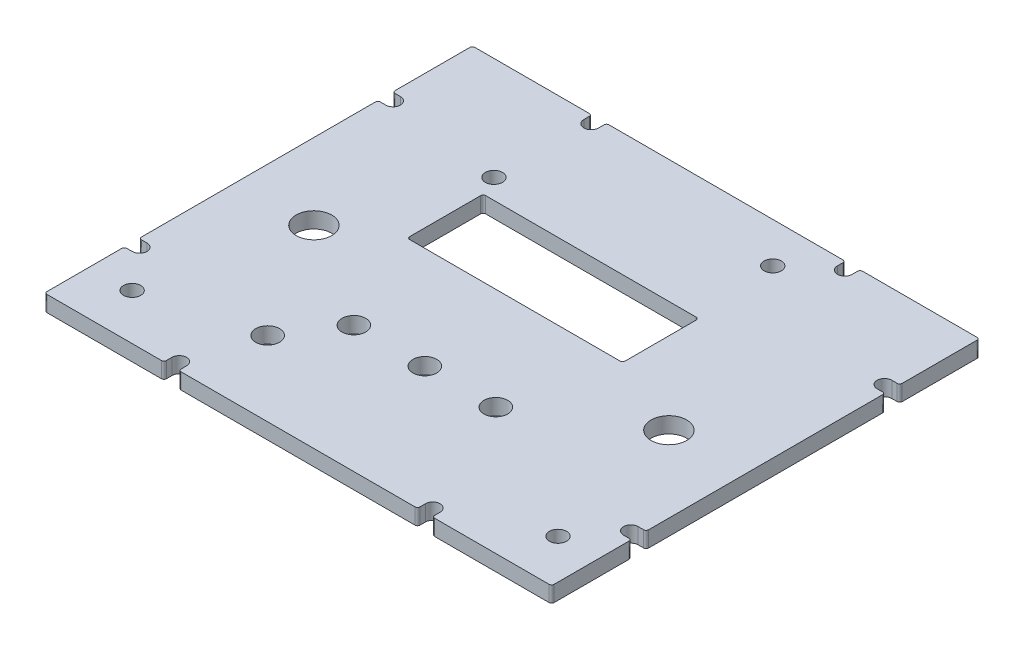
SolidWorks part; units mm, degrees
ref_plane "Front Plane" through (0, 0, 0) normal (0, 0, 1) x (1, 0, 0)
ref_plane "Top Plane" through (0, 0, 0) normal (0, 1, 0) x (1, 0, 0)
ref_plane "Right Plane" through (0, 0, 0) normal (1, 0, 0) x (0, 0, -1)
sketch "Sketch1" plane through (0, 0, 0) normal (0, 1, 0) x (1, 0, 0)
  line L1 (-50.8, -42.8625) -> (50.8, -42.8625)
  line L2 (-50.8, -42.8625) -> (-50.8, 42.8625)
  line L3 (-50.8, 42.8625) -> (50.8, 42.8625)
  line L4 (50.8, -42.8625) -> (50.8, 42.8625)
  line L5 (-50.8, -42.8625) -> (50.8, 42.8625) construction
  line L6 (-50.8, 42.8625) -> (50.8, -42.8625) construction
  point P0 (0, 0)
  dimension "D1" = 101.6
  dimension "D2" = 85.725
extrude "Boss-Extrude1" add sketch "Sketch1" along normal blind 3.175
hole_wizard "#29 (0.136) Diameter Hole1" positions "Sketch2" profile "Sketch3" hole size "#29" standard "ANSI Inch" end condition through all
sketch "Sketch2" plane through (0, 3.175, 0) normal (0, 1, 0) x (1, 0, 0)
  point P0 (-25.8318, 22.2123)
  point P3 (17.4498, 34.7853)
  point P6 (42.8498, -33.6423)
  point P9 (-42.4688, -33.6423)
sketch "Sketch3" plane through (-25.8318, 3.175, -22.2123) normal (1, 0, 0) x (0, 0, 1)
  line L0 (0, 0) -> (0, 3.175)
  line L1 (0, 3.175) -> (1.7272, 3.175)
  line L2 (1.7272, 3.175) -> (1.7272, 0)
  line L5 (1.7272, 0) -> (0, 0)
  line L11 (0, -6.35) -> (0, 107.95) construction
  dimension "Thru Hole Dia." = 3.4544
  dimension "Thru Hole Depth" = 3.175
hole_wizard "9/32 (0.28125) Diameter Hole1" positions "Sketch4" profile "Sketch5" hole size "9/32" standard "ANSI Inch" end condition through all
sketch "Sketch4" plane through (0, 3.175, 0) normal (0, 1, 0) x (1, 0, 0)
  point P0 (-35.56, -4.1275)
  point P3 (35.56, -4.1275)
sketch "Sketch5" plane through (-35.56, 3.175, 4.1275) normal (1, 0, 0) x (0, 0, 1)
  line L0 (0, 0) -> (0, 3.175)
  line L1 (0, 3.175) -> (3.5719, 3.175)
  line L2 (3.5719, 3.175) -> (3.5719, 0)
  line L5 (3.5719, 0) -> (0, 0)
  line L11 (0, -6.35) -> (0, 107.95) construction
  dimension "Thru Hole Dia." = 7.1437
  dimension "Thru Hole Depth" = 3.175
hole_wizard "3/16 (0.1875) Diameter Hole1" positions "Sketch6" profile "Sketch7" hole size "3/16" standard "ANSI Inch" end condition through all
sketch "Sketch6" plane through (0, 3.175, 0) normal (0, 1, 0) x (1, 0, 0)
  point P13 (-14.224, -17.4625)
  point P15 (0, -17.4625)
  point P17 (14.224, -17.4625)
  point P19 (-21.082, -27.8765)
sketch "Sketch7" plane through (-14.224, 3.175, 17.4625) normal (1, 0, 0) x (0, 0, 1)
  line L0 (0, 0) -> (0, 3.175)
  line L1 (0, 3.175) -> (2.3812, 3.175)
  line L2 (2.3812, 3.175) -> (2.3812, 0)
  line L5 (2.3812, 0) -> (0, 0)
  line L11 (0, -6.35) -> (0, 107.95) construction
  dimension "Thru Hole Dia." = 4.7625
  dimension "Thru Hole Depth" = 3.175
sketch "Sketch8" plane through (0, 3.175, 0) normal (0, 1, 0) x (1, 0, 0)
  line L0 (-24.003, 18.2245) -> (19.177, 18.2245)
  line L5 (19.177, 18.2245) -> (19.177, 2.9845)
  line L6 (-24.003, 2.9845) -> (19.177, 2.9845)
  line L7 (-24.003, 18.2245) -> (-24.003, 2.9845)
  circle A0 centre (-25.8318, 22.2123) radius 1.7272 construction
  dimension "D1" = 1.8288
  dimension "D2" = 45.0088
  dimension "D3" = 3.9878
  dimension "D4" = 19.2278
extrude "Cut-Extrude1" cut sketch "Sketch8" against normal through all
sketch "Sketch9" plane through (0, 3.175, 0) normal (0, 1, 0) x (1, 0, 0)
  line L0 (-50.8, 42.8625) -> (50.8, -42.8625) construction
  line L1 (50.8, 42.8625) -> (-50.8, 42.8625) construction
  line L2 (49.2125, -41.275) -> (-49.2125, -41.275) construction
  line L3 (49.2125, -41.275) -> (49.2125, 41.275) construction
  line L4 (49.2125, 41.275) -> (-49.2125, 41.275) construction
  line L5 (-49.2125, -41.275) -> (-49.2125, 41.275) construction
  line L6 (49.2125, -41.275) -> (-49.2125, 41.275) construction
  line L7 (49.2125, 41.275) -> (-49.2125, -41.275) construction
  line L8 (-50.8, 42.8625) -> (-50.8, -42.8625) construction
  line L9 (-49.2125, 26.8732) -> (-50.8, 26.8732)
  line L10 (-49.2125, 23.9268) -> (-50.8, 23.9268)
  line L11 (-50.8, 26.8732) -> (-50.8, 23.9268)
  line L12 (-49.2125, -23.9268) -> (-50.8, -23.9268)
  line L13 (-50.8, -23.9268) -> (-50.8, -26.8732)
  line L14 (-49.2125, -26.8732) -> (-50.8, -26.8732)
  line L15 (0, 0) -> (0, 12.7264) construction
  line L16 (49.2125, -26.8732) -> (50.8, -26.8732)
  line L17 (50.8, -23.9268) -> (50.8, -26.8732)
  line L18 (49.2125, -23.9268) -> (50.8, -23.9268)
  line L19 (50.8, 26.8732) -> (50.8, 23.9268)
  line L20 (49.2125, 23.9268) -> (50.8, 23.9268)
  line L21 (49.2125, 26.8732) -> (50.8, 26.8732)
  line L23 (-24.003, 2.9845) -> (19.177, 2.9845) construction
  arc A0 (-49.2125, 23.9268) -> (-49.2125, 26.8732) centre (-49.2125, 25.4) ccw
  arc A1 (-49.2125, -26.8732) -> (-49.2125, -23.9268) centre (-49.2125, -25.4) ccw
  arc A2 (49.2125, -26.8732) -> (49.2125, -23.9268) centre (49.2125, -25.4) cw
  arc A3 (49.2125, 23.9268) -> (49.2125, 26.8732) centre (49.2125, 25.4) cw
  point P4 (0, 0)
  point P16 (-49.2125, 0)
  dimension "D3" = 25.4
  dimension "D5" = 1.4732
  dimension "D1" = 1.5875
  dimension "D2" = 1.5875
  dimension "D6" = 28.3845
  dimension "D4" = 2
extrude "Cut-Extrude2" cut sketch "Sketch9" against normal through all
fillet "Fillet1" radius 0.508 12 edges at (50.8, 1.5875, -23.9268) (50.8, 1.5875, -26.8732) (50.8, 1.5875, 23.9268) (50.8, 1.5875, 26.8732) (-50.8, 1.5875, 23.9268) (-50.8, 1.5875, 26.8732) (-50.8, 1.5875, -23.9268) (-50.8, 1.5875, -26.8732) (-24.003, 1.5875, -2.9845) (19.177, 1.5875, -2.9845) (19.177, 1.5875, -18.2245) (-24.003, 1.5875, -18.2245)
sketch "Sketch10" plane through (0, 3.175, 0) normal (0, 1, 0) x (1, 0, 0)
  line L0 (-50.8, -42.8625) -> (50.8, -42.8625) construction
  line L1 (49.2125, 41.275) -> (-49.2125, 41.275) construction
  line L2 (49.2125, 41.275) -> (49.2125, -41.275) construction
  line L3 (49.2125, -41.275) -> (26.8732, -41.275) construction
  line L4 (-49.2125, 41.275) -> (-49.2125, -41.275) construction
  line L5 (49.2125, 41.275) -> (-49.2125, -41.275) construction
  line L6 (49.2125, -41.275) -> (-49.2125, 41.275) construction
  line L7 (50.8, -23.4188) -> (50.8, 23.4188) construction
  line L8 (0, 0) -> (-50.8, 0) construction
  line L9 (-50.8, 23.4188) -> (-50.8, -23.4188) construction
  line L10 (0, 0) -> (0, -42.8625) construction
  line L11 (-26.8732, -41.275) -> (-49.2125, -41.275) construction
  line L12 (-23.9268, 41.275) -> (-23.9268, 42.8625)
  line L13 (26.8732, -41.275) -> (26.8732, -42.8625)
  line L14 (26.8732, -42.8625) -> (23.9268, -42.8625)
  line L15 (23.9268, -41.275) -> (23.9268, -42.8625)
  line L16 (23.9268, -41.275) -> (-23.9268, -41.275) construction
  line L17 (-23.9268, -41.275) -> (-23.9268, -42.8625)
  line L18 (-23.9268, -42.8625) -> (-26.8732, -42.8625)
  line L19 (-26.8732, -41.275) -> (-26.8732, -42.8625)
  line L20 (-23.9268, 42.8625) -> (-26.8732, 42.8625)
  line L21 (-26.8732, 41.275) -> (-26.8732, 42.8625)
  line L22 (26.8732, 42.8625) -> (23.9268, 42.8625)
  line L23 (26.8732, 41.275) -> (26.8732, 42.8625)
  line L24 (23.9268, 41.275) -> (23.9268, 42.8625)
  arc A0 (26.8732, -41.275) -> (23.9268, -41.275) centre (25.4, -41.275) ccw
  arc A1 (-23.9268, -41.275) -> (-26.8732, -41.275) centre (-25.4, -41.275) ccw
  arc A2 (-23.9268, 41.275) -> (-26.8732, 41.275) centre (-25.4, 41.275) cw
  arc A3 (26.8732, 41.275) -> (23.9268, 41.275) centre (25.4, 41.275) cw
  point P0 (0, 0)
  dimension "D3" = 2.9464
  dimension "D4" = 25.4
  dimension "D5" = 25.4
  dimension "D1" = 1.5875
  dimension "D2" = 1.5875
extrude "Cut-Extrude3" cut sketch "Sketch10" against normal through all
fillet "Fillet2" radius 0.508 12 edges at (26.8732, 1.5875, -42.8625) (23.9268, 1.5875, -42.8625) (-26.8732, 1.5875, -42.8625) (-23.9268, 1.5875, -42.8625) (-23.9268, 1.5875, 42.8625) (-26.8732, 1.5875, 42.8625) (23.9268, 1.5875, 42.8625) (26.8732, 1.5875, 42.8625) (50.8, 1.5875, 42.8625) (50.8, 1.5875, -42.8625) (-50.8, 1.5875, -42.8625) (-50.8, 1.5875, 42.8625)
